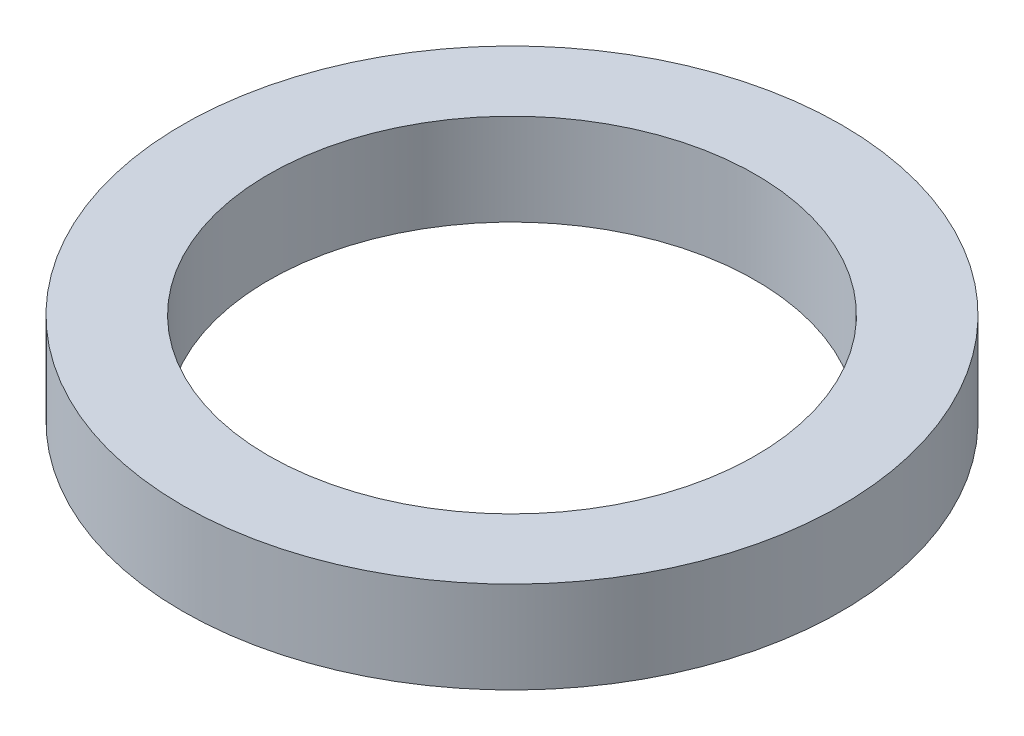
SolidWorks part; units mm, degrees
ref_plane "Front Plane" through (0, 0, 0) normal (0, 0, 1) x (1, 0, 0)
ref_plane "Top Plane" through (0, 0, 0) normal (0, 1, 0) x (1, 0, 0)
ref_plane "Right Plane" through (0, 0, 0) normal (1, 0, 0) x (0, 0, -1)
sketch "Sketch1" plane through (0, 0, 0) normal (0, 1, 0) x (1, 0, 0)
  circle A0 centre (0, 0) radius 57.5
  dimension "FLANGE_OD" = 115
extrude "Boss-Extrude1" add sketch "Sketch1" along normal blind 16
sketch "Sketch2" plane through (0, 0, 0) normal (0, 1, 0) x (1, 0, 0)
  circle A0 centre (0, 0) radius 42.5
  dimension "BORE_D" = 85
extrude "Cut-Extrude1" cut sketch "Sketch2" along normal through all
sketch "Sketch3" plane through (0, 16, 0) normal (0, 1, 0) x (1, 0, 0)
  circle A0 centre (0, 0) radius 23.6373 construction
  circle A1 centre (-23.6373, 0) radius 2.4571
  dimension "BOLT_D" = 4.9141
  dimension "BOLT_PCD" = 47.2746
extrude "Cut-Extrude2" cut sketch "Sketch3" against normal blind 12.8956 rebuild error yes
pattern_circular "CirPattern1" count 6 over 360 rebuild error yes
